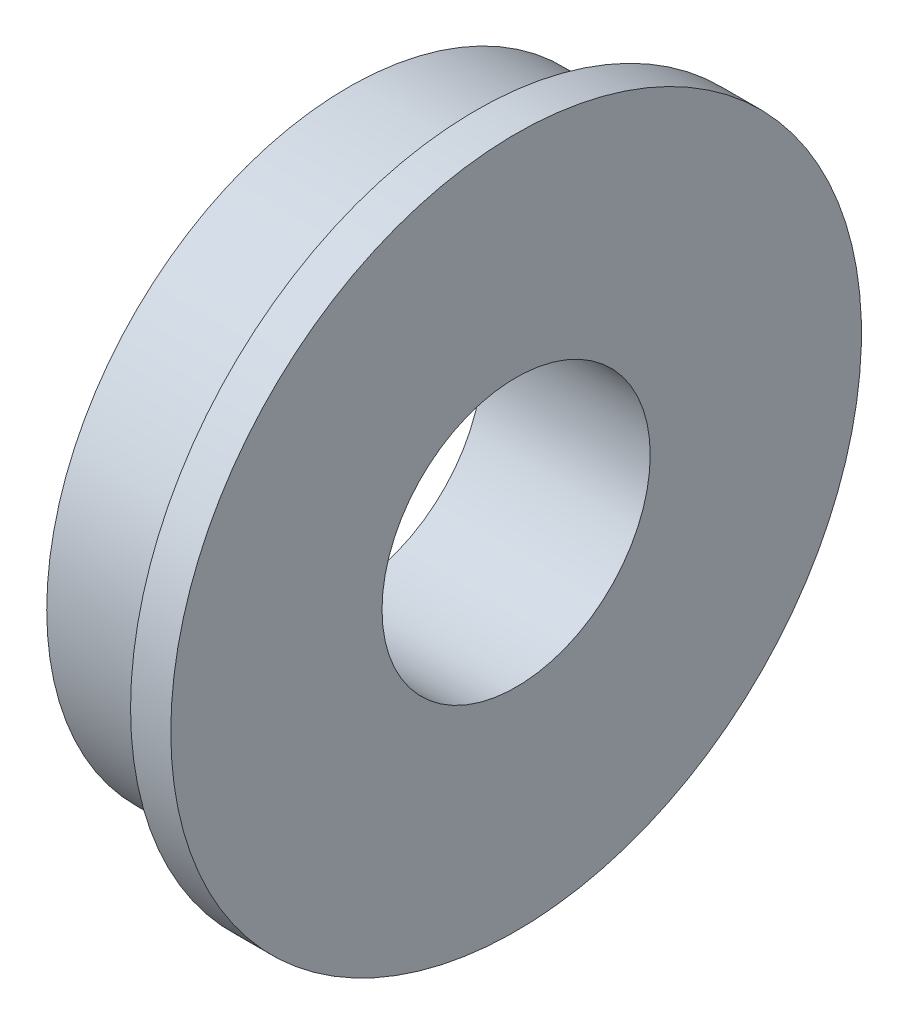
SolidWorks part; units mm, degrees
ref_plane "Plan de face" through (0, 0, 0) normal (0, 0, 1) x (1, 0, 0)
ref_plane "Plan de dessus" through (0, 0, 0) normal (0, 1, 0) x (1, 0, 0)
ref_plane "Plan de droite" through (0, 0, 0) normal (1, 0, 0) x (0, 0, -1)
sketch "Esquisse1" plane through (0, 0, 0) normal (0, 0, 1) x (1, 0, 0)
  line L0 (0, 2) -> (2.5, 2)
  line L1 (2.5, 2) -> (2.5, 5.15)
  line L2 (2.5, 5.15) -> (1.9, 5.15)
  line L3 (1.9, 5.15) -> (1.9, 4.5)
  line L4 (1.9, 4.5) -> (0, 4.5)
  line L5 (0, 4.5) -> (0, 2)
  line L6 (0, 0) -> (2.5, 0) construction
  dimension "D1" = 2
  dimension "D2" = 4.5
  dimension "D3" = 2.5
  dimension "D4" = 5.15
  dimension "D5" = 0.6
revolve "Révolution1" add sketch "Esquisse1" angle 360 about L6
